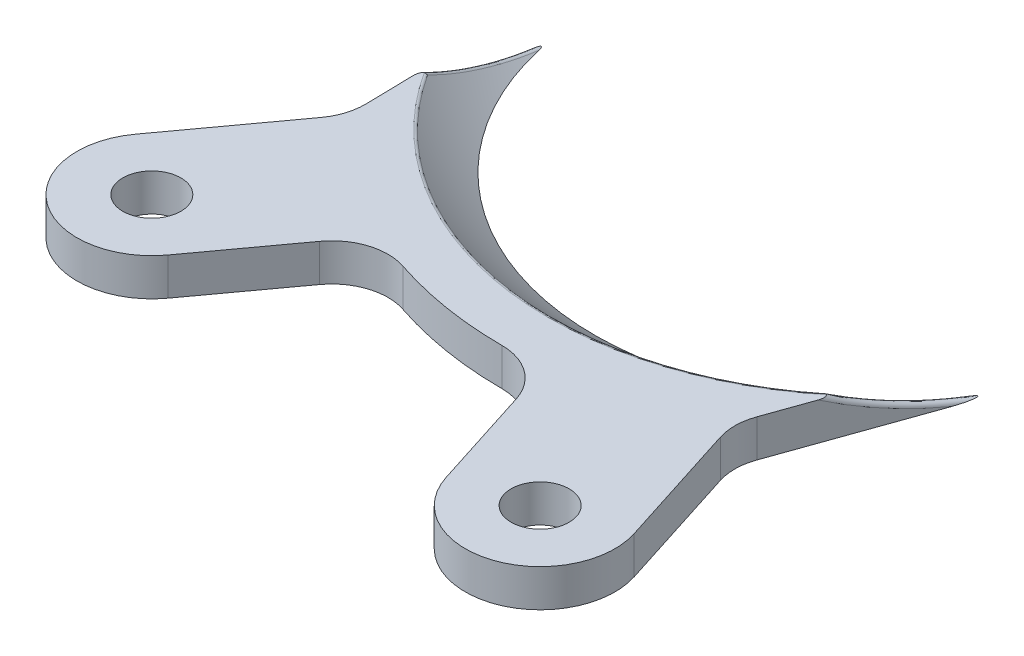
SolidWorks part; units mm, degrees
ref_plane "前视基准面" through (0, 0, 0) normal (0, 0, 1) x (1, 0, 0)
ref_plane "上视基准面" through (0, 0, 0) normal (0, 1, 0) x (1, 0, 0)
ref_plane "右视基准面" through (0, 0, 0) normal (1, 0, 0) x (0, 0, -1)
other "Configuration Table"
sketch "草图1" plane through (0, 0, 0) normal (0, 1, 0) x (1, 0, 0)
  line L0 (-9.4276, 12.118) -> (-14.206, 5.5725)
  line L1 (-7.7445, 0.8555) -> (-2.9662, 7.401)
  line L2 (5.3573, 25.5867) -> (-10.9753, 3.214)
  line L3 (9.974, -2.0172) -> (7.5085, 5.7028)
  line L4 (17.5948, 0.4166) -> (15.1293, 8.1366)
  line L5 (13.7844, -0.8003) -> (5.3573, 25.5867)
  line L6 (15.1293, 8.1366) -> (19.5389, 20.5484)
  line L7 (-9.4276, 12.118) -> (-9.6898, 25.2872)
  circle A0 centre (-10.9753, 3.214) radius 1.55
  circle A1 centre (13.7844, -0.8003) radius 1.55
  circle A2 centre (5.3573, 25.5867) radius 15.05
  circle A3 centre (-10.9753, 3.214) radius 4
  circle A4 centre (13.7844, -0.8003) radius 4
  circle A5 centre (5.3573, 25.5867) radius 20
  dimension "D1" = 3.1
  dimension "D2" = 3.1
  dimension "D3" = 30.1
  dimension "D4" = 40
  dimension "D5" = 8
extrude "凸台-拉伸1" add sketch "草图1" along normal blind 2 contours A3 A0 | A5 L2 A3 L1 | A5 L3 A4 L5 | A4 A1 | A5 L5 A4 L4 | A5 L0 A3 L2 | L7 A5 L2 A2 | A5 L5 A2 L2 | L5 A5 L6 A2 region at (-9.5906, 0, -8.8946) region at (-7.3962, 0, -14.5583) region at (-11.5746, 0, -7.0544) region at (-5.9867, 0, -6.2636) region at (2.6367, 0, -8.8063) region at (13.9729, 0, -11.0937) region at (14.2655, 0, -5.0268) region at (17.6249, 0, 0.2019) region at (10.0149, 0, -3.6693)
fillet "圆角1" radius 3 4 edges at (-9.4276, 1, -12.118) (15.1293, 1, -8.1366) (7.5085, 1, -5.7028) (-2.9662, 1, -7.401)
ref_axis "基准轴1" through (5.3573, 2, -25.5867) along (0, -1, 0)
ref_plane "基准面1" through (5.3573, 0, 0) normal (-1, 0, 0) x (0, -1, 0)
sketch "草图2" plane through (5.3573, 0, 0) normal (-1, 0, 0) x (0, -1, 0)
  line L1 (0, -25.2872) -> (0, -10.5367) construction
  line L2 (-2, -25.5867) -> (0, -25.5867) construction
  line L3 (5.03, -25.5867) -> (-45.03, -25.5867)
  line L4 (0, -25.5867) -> (0, -10.5367) construction
  arc A0 (5.03, -25.5867) -> (-45.03, -25.5867) centre (-20, -25.5867) ccw
  dimension "D2" = 20
  dimension "D1" = 15.05
revolve "切除-旋转1" cut sketch "草图2" angle 360 about L3
fillet "圆角2" radius 0.2 3 edges at (-9.6008, 0.5064, -20.816) (2.5737, 2, -8.4183) (18.0417, 0.5064, -16.3343)
sketch "草图3" plane through (0, 0, 0) normal (0, -1, 0) x (1, 0, 0)
  line L0 (-8.0271, -7.2524) -> (-10.9753, -3.214) construction
  line L1 (-10.0241, -11.3009) -> (-14.206, -5.5725) construction
  circle A0 centre (-8.0271, -7.2524) radius 0.75
  dimension "D1" = 1.5
  dimension "D2" = 5
extrude "切除-拉伸1" cut sketch "草图3" against normal blind 1
